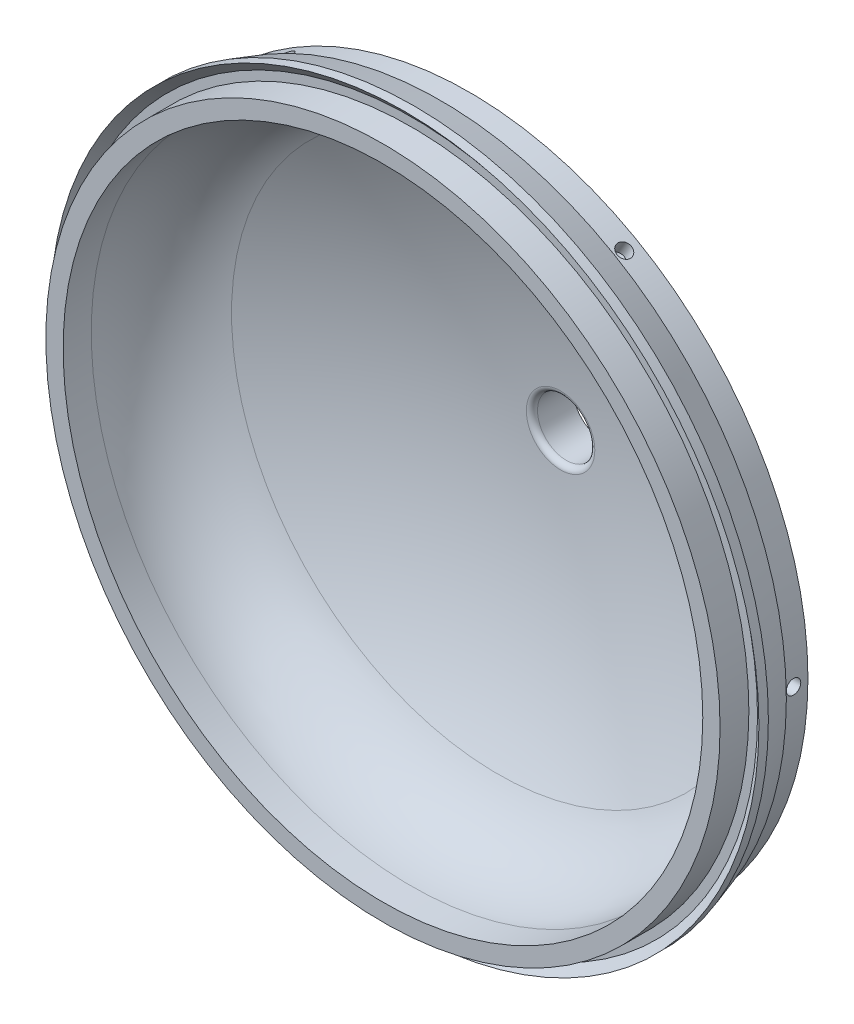
SolidWorks part; units mm, degrees
material "6061-T6 (SS)"
ref_plane "Front Plane" through (0, 0, 0) normal (0, 0, 1) x (1, 0, 0)
ref_plane "Top Plane" through (0, 0, 0) normal (0, 1, 0) x (1, 0, 0)
ref_plane "Right Plane" through (0, 0, 0) normal (1, 0, 0) x (0, 0, -1)
sketch "Sketch1" plane through (0, 0, 0) normal (0, 1, 0) x (1, 0, 0)
  line L0 (0, 0) -> (-140.97, 0) construction
  line L1 (-140.97, 0) -> (-148.59, 0)
  line L2 (-148.59, 0) -> (-148.59, 12.7)
  line L7 (0, 0) -> (0, 12.391) construction
  line L8 (0, 78.7237) -> (0, 85.0737)
  line L9 (-140.97, 0) -> (-140.97, 12.391)
  line L10 (98.044, 12.391) -> (-98.044, 12.391) construction
  line L29 (-152.4, 12.7) -> (-152.4, 9.503) construction
  line L30 (-152.4, 9.503) -> (-156.21, 9.503) construction
  line L31 (-152.4, 25.4) -> (-156.21, 13.674)
  line L32 (-152.4, 12.7) -> (-156.21, 9.503)
  line L33 (-152.4, 25.4) -> (-156.21, 25.4) construction
  line L34 (-156.21, 13.674) -> (-156.21, 25.4) construction
  line L35 (-152.4, 25.4) -> (-149.225, 25.4)
  line L36 (-152.4, 12.7) -> (-152.4, 25.4) construction
  line L37 (-149.225, 25.4) -> (-149.225, 38.1)
  line L38 (-149.225, 38.1) -> (-140.0818, 38.1)
  line L39 (-152.4, 12.7) -> (-148.59, 12.7)
  line L40 (-156.21, 13.674) -> (-156.21, 9.503)
  line L41 (0, 0) -> (0, 85.725) construction
  arc A7 (-115.4202, 51.6429) -> (-140.97, 12.391) centre (-98.044, 12.391) ccw
  arc A9 (-120.3033, 56.353) -> (-140.0818, 38.1) centre (-98.044, 12.391) ccw
  circle A11 centre (-98.044, 12.391) radius 217.043 construction
  circle A14 centre (98.044, 12.391) radius 217.043 construction
  arc A15 (0, 78.7237) -> (-117.4348, 50.6878) centre (0, -181.2453) ccw
  arc A16 (0, 85.0737) -> (-120.3033, 56.353) centre (0, -181.2453) ccw
  point P19 (0, 12.391)
  dimension "D19" = 42.926
  dimension "D20" = 259.969
  dimension "D21" = 266.319
  dimension "D22" = 266.319
  dimension "D11" = 12.391
  dimension "D13" = 434.086
  dimension "D14" = 434.086
  dimension "D16" = 49.276
  dimension "D2" = 3.81
  dimension "D3" = 7.62
  dimension "D4" = 12.7
  dimension "D5" = 3.81
  dimension "D6" = 3.81
  dimension "D7" = 18
  dimension "D8" = 85.725
  dimension "D9" = 50
  dimension "D10" = 152.4
  dimension "D12" = 3.175
  dimension "D15" = 12.7
  dimension "D17" = 25.4
  dimension "D18" = 196.088
ref_axis "Axis1" through (0, 0, 5.4731) along (0, 0, -1)
revolve "Revolve1" add sketch "Sketch1" angle 360 about L8 region at (-144.78, 0, -1.7787)
ref_plane "Plane1" through (0, 0, -86.36) normal (0, 0, 1) x (1, 0, 0)
sketch "Sketch6" plane through (0, 0, -86.36) normal (0, 0, 1) x (1, 0, 0)
  circle A0 centre (76.2, 0) radius 25.4
  circle A2 centre (-76.2, 0) radius 21.515
  dimension "D1" = 152.4
  dimension "D2" = 43.03
  dimension "D3" = 50.8
  dimension "D4" = 76.2
ref_plane "Plane3" through (0, 0, -101.6) normal (0, 0, 1) x (1, 0, 0)
ref_plane "Plane4" through (0, 0, -96.52) normal (0, 0, 1) x (1, 0, 0)
sketch "Sketch10" plane through (0, 0, -96.52) normal (0, 0, 1) x (1, 0, 0)
  circle A0 centre (0, 0) radius 25.4
  dimension "D1" = 50.8
extrude "Boss-Extrude2" add sketch "Sketch10" along normal up to surface (19.0401 mm away) up to face at (117.4348, 0, -50.6878)
sketch "Sketch11" plane through (0, 0, 0) normal (0, 0, 1) x (1, 0, 0)
  circle A0 centre (0, 0) radius 12.7
  dimension "D1" = 25.4
extrude "Cut-Extrude1" cut sketch "Sketch11" against normal blind 190.754 contours A0
ref_plane "Plane5" through (149.225, 0, 0) normal (1, 0, 0) x (0, 0, -1)
sketch "Sketch13" plane through (149.225, 0, 0) normal (1, 0, 0) x (0, 0, -1)
  line L0 (25.4, 0) -> (38.1, 0) construction
  line L1 (25.4, -149.225) -> (25.4, 149.225) construction
  line L2 (38.1, -140.0818) -> (38.1, 140.0818) construction
  circle A0 centre (31.75, 0) radius 3.175
  point P10 (31.75, 0)
  dimension "D1" = 6.35
hole_wizard "1/4 (0.25) Diameter Hole1" positions "Sketch14" profile "Sketch15" hole size "1/4" standard "ANSI Inch"
sketch "Sketch14" plane through (149.225, 0, 0) normal (1, 0, 0) x (0, 0, -1)
  point P0 (31.75, 0)
sketch "Sketch15" plane through (149.225, 0, -31.75) normal (0, 1, 0) x (0, 0, -1)
  line L0 (0, 0) -> (0, 8.2577)
  line L1 (0, 8.2577) -> (3.175, 6.35)
  line L2 (3.175, 6.35) -> (3.175, 0)
  line L5 (3.175, 0) -> (0, 0)
  line L10 (0, 8.2577) -> (-3.175, 6.35) construction
  line L11 (0, -6.35) -> (0, 107.95) construction
  dimension "Hole Dia." = 6.35
  dimension "Hole Depth" = 6.35
  dimension "Drill Angle" = 118
pattern_circular "CirPattern1" count 6 over 360 about axis through (0, 0, 5.4731) along (0, 0, -1) of "1/4 (0.25) Diameter Hole1"
fillet "Fillet1" radius 2.54 1 edges at (12.7, 0, -78.4133)
ref_plane "Plane6" through (142.875, 0, 0) normal (1, 0, 0) x (0, 0, -1)
